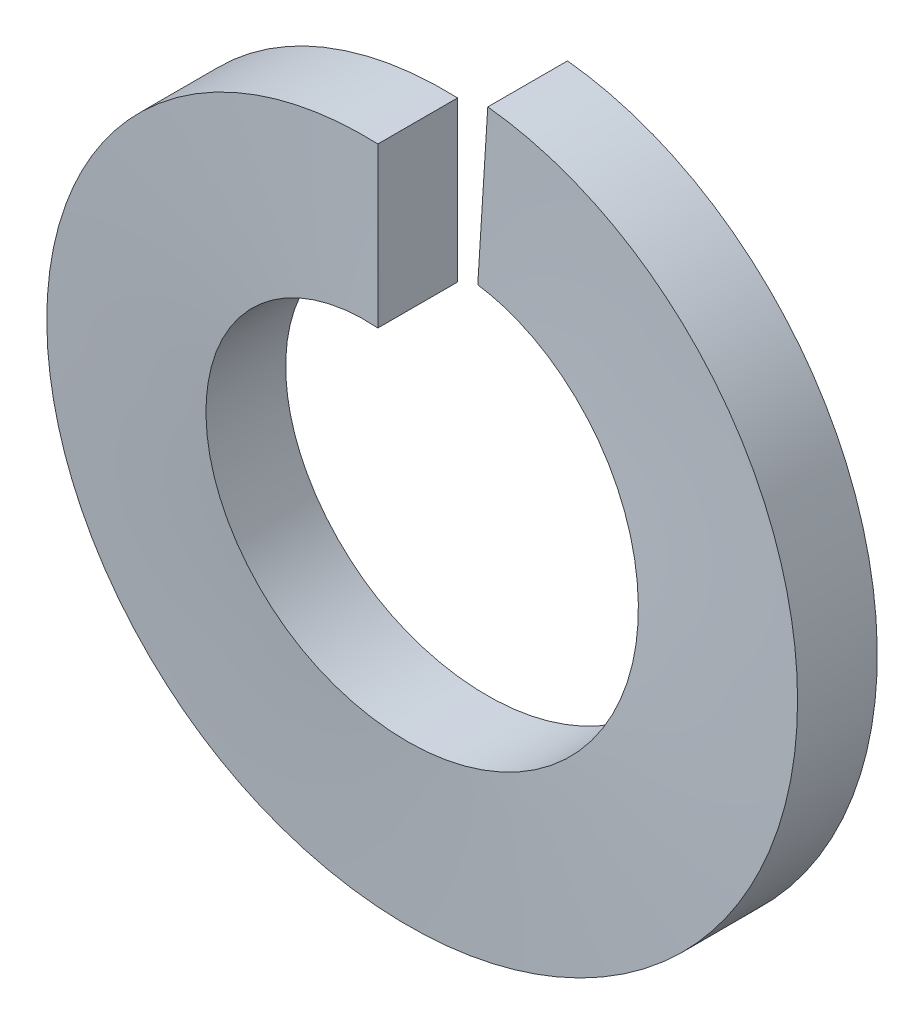
SolidWorks part; units mm, degrees
ref_plane "Front Plane" through (0, 0, 0) normal (0, 0, 1) x (1, 0, 0)
ref_plane "Top Plane" through (0, 0, 0) normal (0, 1, 0) x (1, 0, 0)
ref_plane "Right Plane" through (0, 0, 0) normal (1, 0, 0) x (0, 0, -1)
sketch "Sketch1" plane through (0, 0, 0) normal (0, 0, 1) x (1, 0, 0)
  line L0 (0, 3.1) -> (0, 1.7) construction
  circle A0 centre (0, 0) radius 3.1
  circle A1 centre (0, 0) radius 1.7 construction
  dimension "ID" = 3.4
  dimension "OD" = 6.2
curve "Helix/Spiral1" pitch 0.7778 height 0.77 radius 3.1 left hand yes centre (0, 0, 0) axis (0, 0, -1) start towards (0, 1, 0) parameters "HT"=0.77
sketch "Sketch2" plane through (0, 0, 0) normal (1, 0, 0) x (0, 0, -1)
  line L1 (0, 3.1) -> (-0.7, 3.1)
  line L2 (0, 3.1) -> (0, 1.7)
  line L3 (0, 1.7) -> (-0.7, 1.7)
  line L4 (-0.7, 3.1) -> (-0.7, 1.7)
  dimension "THK" = 0.7
sweep "Sweep1" add profiles "Sketch2" path "Helix/Spiral1"
equation "\"HT@Helix/Spiral1\" = \"THK@Sketch2\"*1.1"
